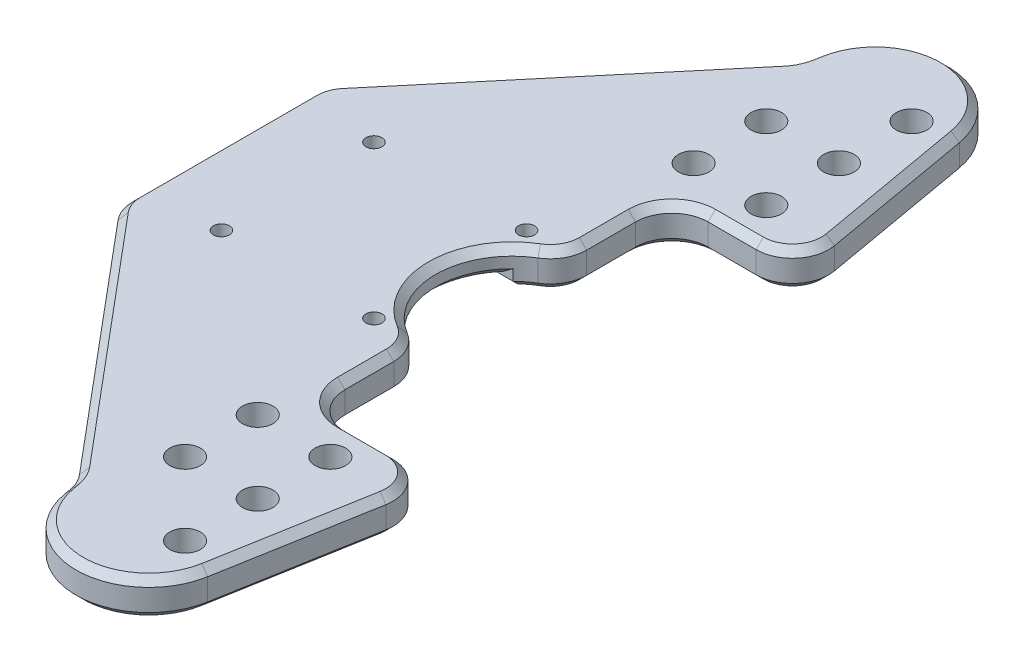
SolidWorks part; units mm, degrees
ref_plane "前视基准面" through (0, 0, 0) normal (0, 0, 1) x (1, 0, 0)
ref_plane "上视基准面" through (0, 0, 0) normal (0, 1, 0) x (1, 0, 0)
ref_plane "右视基准面" through (0, 0, 0) normal (1, 0, 0) x (0, 0, -1)
other "Configuration Table"
sketch "草图1" plane through (0, 0, 0) normal (0, 1, 0) x (1, 0, 0)
  line L0 (0, -25) -> (95.6592, -25) construction
  line L1 (0, -25) -> (0, -50) construction
  line L4 (13.5277, -30.8682) -> (9.8481, -51.7365)
  line L5 (-10.0179, -50.7734) -> (-9.8481, -51.7365)
  line L6 (8.6037, -25) -> (2, -25)
  line L7 (0, 0) -> (95.6592, 0) construction
  line L8 (0, 25) -> (0, 50) construction
  line L9 (8.6037, 25) -> (2, 25)
  line L10 (-10.0179, 50.7734) -> (-9.8481, 51.7365)
  line L11 (13.5277, 30.8682) -> (9.8481, 51.7365)
  line L12 (-11.1117, -48.4277) -> (-38.8302, -15.3941)
  line L13 (-40, -12.1801) -> (-40, 12.1801)
  line L14 (-38.8302, 15.3941) -> (-11.1117, 48.4277)
  line L15 (-3, 20) -> (-3, 13.2759)
  line L16 (-3, -13.2759) -> (-3, -20)
  arc A1 (-9.8481, -51.7365) -> (9.8481, -51.7365) centre (0, -50) ccw
  arc A4 (13.5277, -30.8682) -> (8.6037, -25) centre (8.6037, -30) ccw
  arc A7 (13.5277, 30.8682) -> (8.6037, 25) centre (8.6037, 30) cw
  arc A8 (-9.8481, 51.7365) -> (9.8481, 51.7365) centre (0, 50) cw
  arc A9 (-5.4194, 8.9934) -> (-5.4194, -8.9934) centre (0, 0) ccw
  arc A10 (-5.4194, 8.9934) -> (-3, 13.2759) centre (-8, 13.2759) ccw
  arc A11 (-3, -13.2759) -> (-5.4194, -8.9934) centre (-8, -13.2759) ccw
  arc A12 (2, -25) -> (-3, -20) centre (2, -20) cw
  arc A13 (-3, 20) -> (2, 25) centre (2, 20) cw
  arc A14 (-11.1117, 48.4277) -> (-10.0179, 50.7734) centre (-14.9419, 51.6417) ccw
  arc A15 (-11.1117, -48.4277) -> (-10.0179, -50.7734) centre (-14.9419, -51.6417) cw
  arc A16 (-38.8302, -15.3941) -> (-40, -12.1801) centre (-35, -12.1801) cw
  arc A17 (-40, 12.1801) -> (-38.8302, 15.3941) centre (-35, 12.1801) cw
  point P6 (14.5624, -25)
  point P25 (14.5624, 25)
  point P44 (-40, -14)
  point P47 (-40, 14)
  dimension "D2" = 10
  dimension "D3" = 80
  dimension "D4" = 5
  dimension "D8" = 21
  dimension "D12" = 5
  dimension "D5" = 50
  dimension "D6" = 3
  dimension "D7" = 28
  dimension "D9" = 40
  dimension "D10" = 50
  dimension "D11" = 50
extrude "凸台-拉伸1" add sketch "草图1" along normal mid plane 5
sketch "草图2" plane through (0, 2.5, 0) normal (0, 1, 0) x (1, 0, 0)
  line L0 (0, 0) -> (70.816, 0) construction
  line L1 (0, -50) -> (0, 50) construction
  line L2 (5, -50) -> (0, -50) construction
  circle A1 centre (5, -50) radius 2.1
  circle A2 centre (5, 50) radius 2.1
  dimension "D1" = 4.2
  dimension "D2" = 5
extrude "切除-拉伸1" cut sketch "草图2" against normal through all
sketch "草图3" plane through (0, -2.5, 0) normal (0, -1, 0) x (1, 0, 0)
  line L1 (0, 0) -> (-61.6695, 0) construction
  line L6 (-29.5, 10.5) -> (-8.5, 10.5) construction
  line L7 (-29.5, -10.5) -> (-8.5, -10.5) construction
  circle A2 centre (-8.5, 10.5) radius 1.1
  circle A3 centre (-29.5, 10.5) radius 1.1
  circle A6 centre (-29.5, -10.5) radius 1.1
  circle A7 centre (-8.5, -10.5) radius 1.1
  point P8 (0, 0)
  dimension "D3" = 21
  dimension "D1" = 2.2
  dimension "D2" = 8.5
  dimension "D4" = 21
extrude "切除-拉伸2" cut sketch "草图3" against normal through all
sketch "草图6" plane through (0, -2.5, 0) normal (0, -1, 0) x (1, 0, 0)
  line L0 (0, 0) -> (-48.2013, 0) construction
  line L2 (-36, -7.5) -> (0, -7.5)
  line L3 (-36, -7.5) -> (-36, 7.5)
  line L4 (-36, 7.5) -> (0, 7.5)
  line L5 (0, -7.5) -> (0, 7.5)
  line L6 (-36, -7.5) -> (0, 7.5) construction
  line L7 (-36, 7.5) -> (0, -7.5) construction
  point P3 (-18, 0)
  dimension "D1" = 15
  dimension "D2" = 36
extrude "切除-拉伸3" cut sketch "草图6" against normal blind 1.5
chamfer "倒角1" distance 1 angle 45 52 edges at (-9.933, 2.5, 51.255) (0, 2.5, 60) (11.6879, 2.5, 41.3024) (-9.933, -2.5, 51.255) (0, -2.5, 60) (11.6879, -2.5, 41.3024) (5.3018, 2.5, 25) (12.4339, 2.5, 26.7861) (12.4339, -2.5, 26.7861) (5.3018, -2.5, 25) (-9.933, -2.5, -51.255) (-10.4104, -2.5, -49.5286) (0, -2.5, -60) (-24.971, -2.5, -31.9109) (11.6879, -2.5, -41.3024) (-39.6985, -2.5, -13.8902) (12.4339, -2.5, -26.7861) (5.3018, -2.5, -25) (-39.6985, -2.5, 13.8902) (-1.5355, -2.5, -23.5355) (-24.971, -2.5, 31.9109) (-3, -2.5, -16.638) (-10.4104, -2.5, 49.5286) (-3.6467, -2.5, -10.8166) (-3.6467, -2.5, 10.8166) (-3, -2.5, 16.638) (-1.5355, -2.5, 23.5355) (11.6879, 2.5, -41.3024) (0, 2.5, -60) (12.4339, 2.5, -26.7861) (-9.933, 2.5, -51.255) (5.3018, 2.5, -25) (-10.4104, 2.5, -49.5286) (-1.5355, 2.5, -23.5355) (-24.971, 2.5, -31.9109) (-3, 2.5, -16.638) (-39.6985, 2.5, -13.8902) (-3.6467, 2.5, -10.8166) (-40, 2.5, 0) (-10.5, 2.5, 0) (-39.6985, 2.5, 13.8902) (-3.6467, 2.5, 10.8166) (-24.971, 2.5, 31.9109) (-3, 2.5, 16.638) (-10.4104, 2.5, 49.5286) (-1.5355, 2.5, 23.5355) (-40, -2.5, 0) (-10.5, -1, 0) (-6.4274, -2.5, -8.3029) (-21.6742, -2.5, -7.5) (-21.6742, -2.5, 7.5) (-36, -2.5, 0)
sketch "草图7" plane through (0, 2.5, 0) normal (0, 1, 0) x (1, 0, 0)
  line L0 (0, 0) -> (79.0215, 0) construction
  line L1 (0, -50) -> (0, 50) construction
  line L2 (-5, 30) -> (5, 30) construction
  line L3 (-5, -30) -> (5, -30) construction
  circle A0 centre (-5, 40) radius 2.1
  circle A1 centre (5, 40) radius 2.1
  circle A2 centre (5, -40) radius 2.1
  circle A3 centre (-5, -40) radius 2.1
  circle A4 centre (-5, 30) radius 2.1
  circle A5 centre (5, 30) radius 2.1
  circle A6 centre (5, -30) radius 2.1
  circle A7 centre (-5, -30) radius 2.1
  dimension "D1" = 4.2
  dimension "D2" = 10
  dimension "D3" = 40
  dimension "D4" = 4.2
  dimension "D5" = 10
  dimension "D6" = 10
extrude "切除-拉伸4" cut sketch "草图7" against normal through all both
